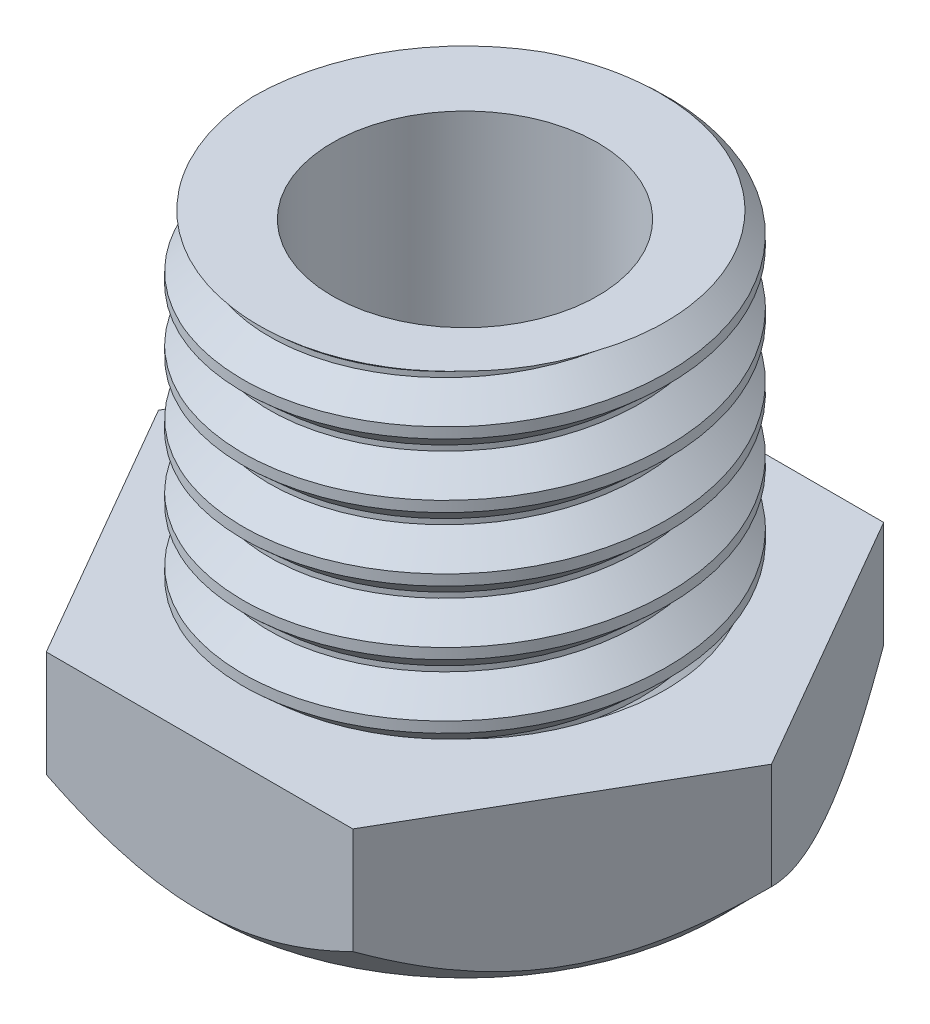
SolidWorks part; units mm, degrees
note: The reader was unsure of these and kept them because the rebuilt part matched: shared geometry of "Sketch1<2>".
ref_plane "Front Plane" through (0, 0, 0) normal (0, 0, 1) x (1, 0, 0)
ref_plane "Top Plane" through (0, 0, 0) normal (0, 1, 0) x (1, 0, 0)
ref_plane "Right Plane" through (0, 0, 0) normal (1, 0, 0) x (0, 0, -1)
sketch "Sketch1" plane through (0, 0, 0) normal (0, 1, 0) x (1, 0, 0)
  line L1 (5.7735, 0) -> (2.8868, 5)
  line L2 (2.8868, 5) -> (-2.8868, 5)
  line L3 (-2.8868, 5) -> (-5.7735, 0)
  line L4 (-5.7735, 0) -> (-2.8868, -5)
  line L5 (-2.8868, -5) -> (2.8868, -5)
  line L6 (2.8868, -5) -> (5.7735, 0)
  circle A0 centre (0, 0) radius 5 construction
  circle A1 centre (0, 0) radius 4
extrude "Boss-Extrude1" add sketch "Sketch1" along normal blind 3
extrude "Boss-Extrude2" add sketch "Sketch1<2>" along normal blind 9 contours A1
sketch "Sketch1<2>" plane through (0, 0, 0) normal (0, 1, 0) x (1, 0, 0) same geometry as "Sketch1"
sketch "Sketch2" plane through (0, 9, 0) normal (0, 1, 0) x (1, 0, 0)
  circle A1 centre (0, 0) radius 4
  circle A2 centre (0, 0) radius 4
  dimension "D1" = 0
curve "Helix/Spiral1" pitch 1.2 height 6 turns 5
sketch "Sketch3" plane through (0, 0, 0) normal (0, 0, 1) x (1, 0, 0)
  line L0 (-4, 9) -> (-3.5, 8.55)
  line L3 (-4, 9) -> (-4, 3) construction
  line L4 (-4, 8) -> (-4.6199, 8)
  line L5 (-4.6199, 8) -> (-4.6199, 9)
  line L6 (-4.6199, 9) -> (-4, 9)
  line L7 (-3.5, 8.55) -> (-3.5, 8.45)
  line L9 (-3.5, 8.45) -> (-4, 8)
  dimension "D1" = 0.5
  dimension "D2" = 1
  dimension "D3" = 0.1
sweep "Cut-Sweep1" cut profiles "Sketch3" path "Helix/Spiral1" align with end faces yes
sketch "Sketch4" plane through (0, 0, 0) normal (0, 0, 1) x (1, 0, 0)
  line L0 (-5.7735, 0) -> (-5.7735, 1)
  line L1 (-5.7735, 3) -> (-5.7735, 0) construction
  line L2 (-5.7735, 1) -> (-4.7735, 0)
  line L3 (-5.7735, 0) -> (-2.8868, 0) construction
  line L4 (-4.7735, 0) -> (-5.7735, 0)
  dimension "D1" = 45
  dimension "D2" = 1
ref_axis "Axis1" through (0, 9, 0) along (0, -1, 0)
revolve "Cut-Revolve1" cut sketch "Sketch4" angle 360 about axis through (0, 9, 0) along (0, -1, 0)
sketch "Sketch5" plane through (0, 9, 0) normal (0, 1, 0) x (1, 0, 0)
  circle A0 centre (0, 0) radius 2.5
  dimension "D1" = 5
extrude "Cut-Extrude1" cut sketch "Sketch5" against normal blind 10
